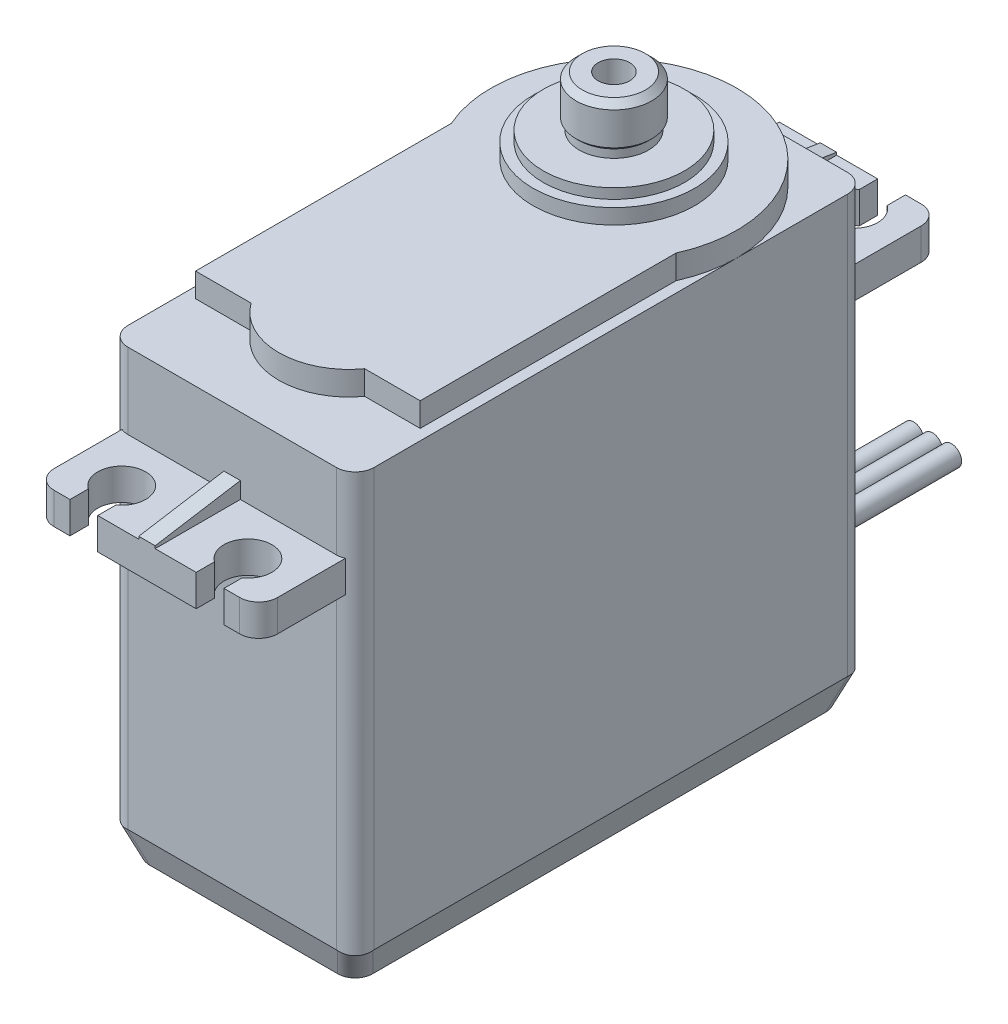
SolidWorks part; units mm, degrees
ref_plane "Front Plane" through (0, 0, 0) normal (0, 0, 1) x (1, 0, 0)
ref_plane "Top Plane" through (0, 0, 0) normal (0, 1, 0) x (1, 0, 0)
ref_plane "Right Plane" through (0, 0, 0) normal (1, 0, 0) x (0, 0, -1)
sketch "Sketch2" plane through (0, 0, 0) normal (0, 1, 0) x (1, 0, 0)
  line L0 (-9.75, 20.25) -> (9.75, -20.25) construction
  line L1 (-9.75, 20.25) -> (9.75, 20.25)
  line L2 (-9.75, 20.25) -> (-9.75, -20.25)
  line L3 (-9.75, -20.25) -> (9.75, -20.25)
  line L4 (9.75, 20.25) -> (9.75, -20.25)
  dimension "D1" = 40.5
  dimension "D2" = 19.5
extrude "Boss-Extrude1" add sketch "Sketch2" along normal mid plane 35.6
chamfer "Chamfer1" distance 2.5 angle 20 4 edges at (0, -17.8, 20.25) (9.75, -17.8, 0) (0, -17.8, -20.25) (-9.75, -17.8, 0)
fillet "Fillet1" radius 1.5 8 edges at (9.75, 1.25, -20.25) (9.75, 1.25, 20.25) (-9.75, 1.25, 20.25) (-9.75, 1.25, -20.25) (-9.295, -16.55, 19.795) (-9.295, -16.55, -19.795) (9.295, -16.55, -19.795) (9.295, -16.55, 19.795)
sketch "Sketch3" plane through (0, 17.8, 0) normal (0, 1, 0) x (1, 0, 0)
  line L0 (-8.85, 27) -> (8.85, -27) construction
  line L1 (-8.85, 27) -> (8.85, 27)
  line L2 (-8.85, 27) -> (-8.85, -27)
  line L3 (-8.85, -27) -> (8.85, -27)
  line L4 (8.85, 27) -> (8.85, -27)
  dimension "D1" = 17.7
  dimension "D2" = 54
extrude "Boss-Extrude2" add sketch "Sketch3" against normal blind 2.5 from offset 6 offset against normal yes
fillet "Fillet2" radius 1.5 4 edges at (8.85, 10.55, 27) (-8.85, 10.55, 27) (8.85, 10.55, -27) (-8.85, 10.55, -27)
sketch "Sketch4" plane through (0, 0, 0) normal (1, 0, 0) x (0, 0, -1)
  line L0 (-20.25, 11.8) -> (-27, 11.8)
  line L1 (-27, 11.8) -> (-27, 12)
  line L2 (-27, 12) -> (-20.25, 13.1)
  line L3 (-20.25, 13.1) -> (-20.25, 11.8)
  line L4 (-27, 11.8) -> (-27, 9.3) construction
  dimension "D1" = 1.3
  dimension "D2" = 0.2
extrude "Boss-Extrude3" add sketch "Sketch4" along normal mid plane 1.3
mirror "Mirror1" about plane through (0, 0, 0) normal (0, 0, 1) of "Boss-Extrude3"
sketch "Sketch5" plane through (0, 17.8, 0) normal (0, 1, 0) x (1, 0, 0)
  line L0 (-9.75, 18.75) -> (-9.75, -18.75) construction
  line L1 (-8.9, 6.0185) -> (-8.9, -14.25)
  line L2 (-8.9, -14.25) -> (-4.5, -14.25)
  line L3 (8.9, -14.25) -> (8.9, 6.0185)
  line L4 (-8.9, -4.1158) -> (8.9, -4.1158) construction
  line L5 (8.25, 20.25) -> (-8.25, 20.25) construction
  line L6 (-8.25, -20.25) -> (8.25, -20.25) construction
  line L7 (4.5, -14.25) -> (8.9, -14.25)
  arc A0 (8.9, 6.0185) -> (-8.9, 6.0185) centre (0, 10) ccw
  arc A1 (-4.5, -14.25) -> (4.5, -14.25) centre (0, -10.9978) ccw
  point P11 (0, 19.75)
  point P19 (0, -16.55)
  dimension "D5" = 2.3
  dimension "D1" = 17.8
  dimension "D2" = 0.5
  dimension "D3" = 6
  dimension "D4" = 9
extrude "Boss-Extrude4" add sketch "Sketch5" along normal blind 1.9
sketch "Sketch6" plane through (0, 19.7, 0) normal (0, 1, 0) x (1, 0, 0)
  circle A0 centre (0, 10) radius 6.4
  dimension "D1" = 12.8
extrude "Boss-Extrude5" add sketch "Sketch6" along normal blind 1.2
sketch "Sketch7" plane through (0, 20.9, 0) normal (0, 1, 0) x (1, 0, 0)
  circle A0 centre (0, 10) radius 5.6
  dimension "D1" = 11.2
extrude "Boss-Extrude6" add sketch "Sketch7" along normal offset from surface (0.8 mm away) 2 up to face at (0, 19.7, -3.6) offset beyond the face yes
sketch "Sketch8" plane through (0, 21.7, 0) normal (0, 1, 0) x (1, 0, 0)
  circle A1 centre (0, 10) radius 2.75
  dimension "D1" = 5.5
extrude "Boss-Extrude7" add sketch "Sketch8" along normal offset from surface (4 mm away) 6 up to face at (0, 19.7, -3.6) offset beyond the face yes
sketch "Sketch9" plane through (0, 25.7, 0) normal (0, 1, 0) x (1, 0, 0)
  circle A0 centre (0, 10) radius 3
  dimension "D1" = 6
extrude "Boss-Extrude8" add sketch "Sketch9" against normal blind 3.4
chamfer "Chamfer2" distance 0.3 angle 45 1 edges at (0, 22.3, -7)
chamfer "Chamfer3" distance 0.5 angle 45 1 edges at (0, 25.7, -7)
sketch "Sketch11" plane through (0, 11.8, 0) normal (0, 1, 0) x (1, 0, 0)
  line L0 (0.65, -27) -> (7.35, -27) construction
  line L1 (6.1, -27) -> (3.9, -27)
  line L2 (5, -24) -> (5, -27) construction
  line L3 (6.1, -25.5492) -> (6.1, -27)
  line L4 (3.9, -25.5492) -> (3.9, -27)
  arc A0 (6.1, -25.5492) -> (3.9, -25.5492) centre (5, -24) ccw
  dimension "D1" = 3.8
  dimension "D2" = 24
  dimension "D3" = 2.2
  dimension "D4" = 5
extrude "Cut-Extrude1" cut sketch "Sketch11" against normal up to next
mirror "Mirror2" about plane through (0, 0, 0) normal (1, 0, 0) of "Cut-Extrude1"
mirror "Mirror3" about plane through (0, 0, 0) normal (0, 0, 1) of "Mirror2", "Cut-Extrude1"
sketch "Sketch12" plane through (0, 0, -20.25) normal (0, 0, 1) x (1, 0, 0)
  line L1 (-3.4, -14.5) -> (3.4, -14.5)
  line L2 (-3.4, -14.5) -> (-3.4, -10.5)
  line L3 (-3.4, -10.5) -> (3.4, -10.5)
  line L4 (3.4, -14.5) -> (3.4, -10.5)
  line L5 (-3.4, -14.5) -> (3.4, -10.5) construction
  line L6 (-3.4, -10.5) -> (3.4, -14.5) construction
  line L7 (0.65, 11.8) -> (8.25, 11.8) construction
  point P0 (0, -12.5)
  dimension "D1" = 6.8
  dimension "D2" = 4
  dimension "D3" = 26.3
extrude "Boss-Extrude9" add sketch "Sketch12" against normal blind 0.8 contours L4 L3 L2 L1
sketch "Sketch13" plane through (0, 0, -21.05) normal (0, 0, -1) x (-1, 0, 0)
  line L14 (-3.2, -10.7) -> (-3.2, -14.3)
  line L15 (-3.2, -14.3) -> (3.2, -14.3)
  line L16 (3.2, -14.3) -> (3.2, -10.7)
  line L17 (3.2, -10.7) -> (-3.2, -10.7)
  line L18 (-3.2, -10.7) -> (-3.2, -14.3)
  line L19 (-3.2, -14.3) -> (3.2, -14.3)
  line L20 (3.2, -14.3) -> (3.2, -10.7)
  line L21 (3.2, -10.7) -> (-3.2, -10.7)
  dimension "D1" = 0.2
extrude "Boss-Extrude10" add sketch "Sketch13" along normal offset from surface 5 draft 3
sketch "Sketch14" plane through (0, 0, -25.25) normal (0, 0, -1) x (-1, 0, 0)
  line L0 (-1.5, -12.5) -> (1.5, -12.5) construction
  line L1 (2.9799, -14.0799) -> (-2.9799, -10.9201) construction
  arc A0 (0.75, -12.7784) -> (0.75, -12.2216) centre (1.5, -12.5) ccw
  arc A1 (0.75, -12.2216) -> (-0.75, -12.2216) centre (0, -12.5) ccw
  arc A2 (-0.75, -12.2216) -> (-0.75, -12.7784) centre (-1.5, -12.5) ccw
  arc A3 (-0.75, -12.7784) -> (0.75, -12.7784) centre (0, -12.5) ccw
  dimension "D1" = 1.6
  dimension "D2" = 3
extrude "Boss-Extrude11" add sketch "Sketch14" along normal blind 10
hole_wizard "M3x0.5 Tapped Hole1" positions "Sketch15" profile "Sketch17" tap size "M3x0.5" standard "ANSI Metric"
sketch "Sketch15" plane through (0, 25.7, 0) normal (0, 1, 0) x (1, 0, 0)
  point P0 (0, 10)
sketch "Sketch17" plane through (0, 25.7, -10) normal (1, 0, 0) x (0, 0, 1)
  line L0 (0, 0) -> (0, 6.7511)
  line L1 (0, 6.7511) -> (1.25, 6)
  line L2 (1.25, 6) -> (1.25, 0)
  line L5 (1.25, 0) -> (0, 0)
  line L10 (0, 6.7511) -> (-1.25, 6) construction
  line L11 (0, -6.35) -> (0, 107.95) construction
  dimension "Tap Drill Dia." = 2.5
  dimension "Tap Drill Depth" = 6
  dimension "Drill Angle" = 118
cosmetic thread "Hole Thread1" parameters "D1"=6, "D2"=3
